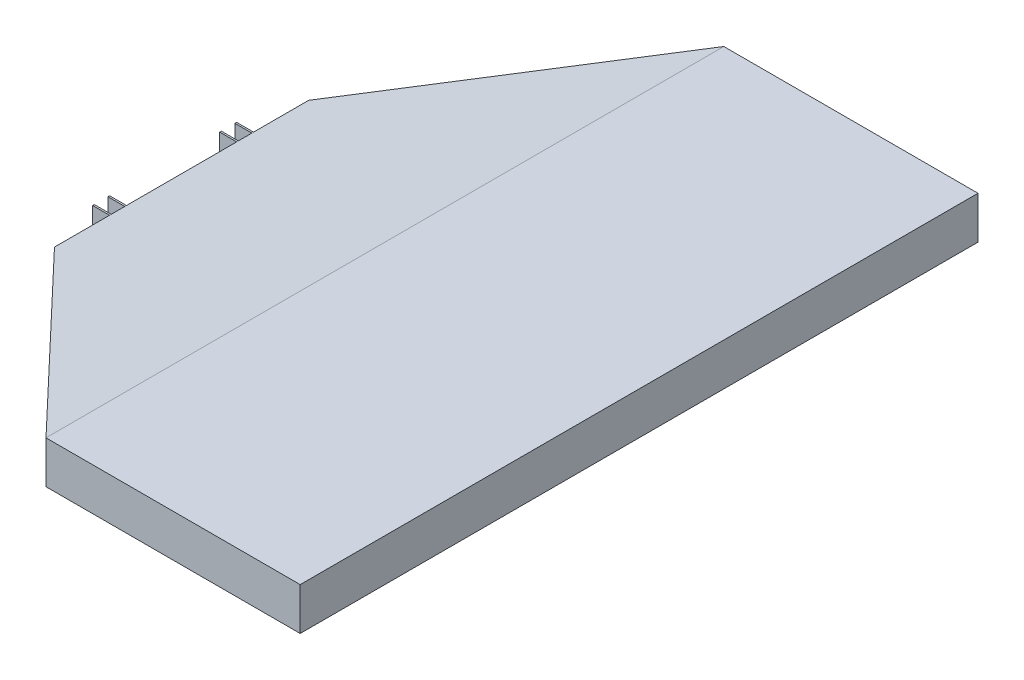
SolidWorks part; units mm, degrees
material "1060 Alloy"
ref_plane "Front Plane" through (0, 0, 0) normal (0, 0, 1) x (1, 0, 0)
ref_plane "Top Plane" through (0, 0, 0) normal (0, 1, 0) x (1, 0, 0)
ref_plane "Right Plane" through (0, 0, 0) normal (1, 0, 0) x (0, 0, -1)
sketch "Sketch1" plane through (0, 0, 0) normal (0, 1, 0) x (1, 0, 0)
  line L1 (3.5148, 13.895) -> (67.0148, 13.895)
  line L2 (3.5148, 13.895) -> (3.5148, -36.905)
  line L3 (3.5148, -36.905) -> (67.0148, -36.905)
  line L4 (67.0148, 13.895) -> (67.0148, -36.905)
  dimension "D1" = 63.5
  dimension "D2" = 50.8
extrude "Boss-Extrude1" add sketch "Sketch1" along normal blind 6.35
sketch "Sketch2" plane through (0, 0, 0) normal (0, 1, 0) x (1, 0, 0)
  line L0 (3.5148, 13.895) -> (3.5148, -36.905)
  line L1 (3.5148, -36.905) -> (-26.9652, -36.905)
  line L4 (-26.9652, -36.905) -> (-26.9652, -17.855)
  line L5 (-26.9652, -17.855) -> (3.5148, 13.895)
  dimension "D1" = 30.48
  dimension "D2" = 19.05
extrude "Boss-Extrude5" add sketch "Sketch2" along normal blind 6.35
sketch "Sketch7" plane through (0, 0, -13.895) normal (0, 0, -1) x (-1, 0, 0)
  line L0 (-3.5148, 6.35) -> (26.9652, 0)
  line L1 (26.9652, 0) -> (26.9652, 6.35)
  line L2 (26.9652, 6.35) -> (-3.5148, 6.35)
extrude "Cut-Extrude3" cut sketch "Sketch7" against normal blind 55.118
sketch "Sketch8" plane through (0, 0, 0) normal (0, -1, 0) x (-1, 0, 0)
  line L0 (26.9652, -17.855) -> (1.5652, -17.855)
  line L1 (1.5652, -17.855) -> (1.5652, -36.905)
  line L2 (26.9652, -36.905) -> (-67.0148, -36.905) construction
  line L3 (26.9652, -17.855) -> (26.9652, -36.905)
  line L4 (26.9652, -36.905) -> (1.5652, -36.905)
  dimension "D1" = 25.4
extrude "Boss-Extrude6" add sketch "Sketch8" along normal blind 2.54
sketch "Sketch11" plane through (0, -2.54, 0) normal (0, -1, 0) x (1, 0, 0)
  line L1 (-26.9652, 36.905) -> (-26.9652, 17.855) construction
  line L2 (-26.9652, 27.38) -> (-26.9652, 28.65)
  line L3 (-26.9652, 27.38) -> (-26.9652, 26.11)
  line L4 (-26.9652, 28.65) -> (-29.5052, 28.65)
  line L5 (-29.5052, 28.65) -> (-29.5052, 26.11)
  line L6 (-29.5052, 26.11) -> (-26.9652, 26.11)
  dimension "D1" = 1.27
  dimension "D2" = 1.27
  dimension "D3" = 2.54
extrude "Boss-Extrude9" add sketch "Sketch11" against normal blind 2.54
sketch "Sketch13" plane through (-29.5052, 0, 0) normal (-1, 0, 0) x (0, 0, 1)
  line L0 (27.38, 0) -> (26.364, 0)
  line L1 (26.11, 0) -> (28.65, 0) construction
  line L2 (27.38, 0) -> (28.396, 0)
  line L3 (26.364, 0) -> (26.364, -2.54)
  line L4 (28.65, -2.54) -> (26.11, -2.54) construction
  line L5 (26.364, -2.54) -> (27.38, -2.54)
  line L6 (27.38, -2.54) -> (28.396, -2.54)
  line L7 (28.396, -2.54) -> (28.396, 0)
  dimension "D1" = 1.016
  dimension "D2" = 1.016
extrude "Cut-Extrude5" cut sketch "Sketch13" against normal blind 2.54
sketch "Sketch14" plane through (0, -2.54, 0) normal (0, -1, 0) x (1, 0, 0)
  line L0 (-14.2652, 36.905) -> (-7.9152, 36.905)
  line L1 (-1.5652, 36.905) -> (-26.9652, 36.905) construction
  line L2 (-14.2652, 36.905) -> (-20.6152, 36.905)
  line L3 (-20.6152, 36.905) -> (-20.6152, 26.745)
  line L4 (-20.6152, 26.745) -> (-7.9152, 26.745)
  line L5 (-7.9152, 26.745) -> (-7.9152, 36.905)
  dimension "D1" = 6.35
  dimension "D2" = 6.35
  dimension "D3" = 10.16
extrude "Boss-Extrude10" add sketch "Sketch14" along normal blind 10.16
sketch "Sketch15" plane through (-20.6152, 0, 0) normal (-1, 0, 0) x (0, 0, 1)
  line L1 (36.905, -12.7) -> (26.745, -12.7) construction
  line L4 (28.015, -12.7) -> (28.015, -11.43)
  line L6 (36.905, -12.7) -> (36.905, -2.54) construction
  line L7 (28.015, -11.43) -> (36.905, -6.35)
  line L8 (28.015, -12.7) -> (36.905, -12.7)
  line L9 (36.905, -12.7) -> (36.905, -6.35)
  dimension "D3" = 1.27
extrude "Cut-Extrude6" cut sketch "Sketch15" against normal blind 12.7
sketch "Sketch16" plane through (0, 0, 17.855) normal (0, 0, -1) x (-1, 0, 0)
  line L0 (22.5202, -2.54) -> (22.5202, 0)
  line L1 (23.7902, -2.54) -> (22.5202, -2.54)
  line L2 (23.7902, -2.54) -> (25.0602, -2.54)
  line L3 (-3.5148, 0) -> (26.9652, 0) construction
  line L4 (22.5202, 0) -> (25.0602, 0)
  line L5 (25.0602, 0) -> (25.0602, -2.54)
  dimension "D1" = 1.27
  dimension "D2" = 1.27
extrude "Boss-Extrude11" add sketch "Sketch16" along normal blind 1.27
extrude "Cut-Extrude7" cut sketch "Sketch16<2>" along normal blind 1.016
sketch "Sketch16<2>" plane through (0, 0, 17.855) normal (0, 0, -1) x (-1, 0, 0) same geometry as "Sketch16"
sketch "Sketch18" plane through (0, 0, 17.855) normal (0, 0, -1) x (-1, 0, 0)
  line L2 (4.7402, -2.54) -> (3.4702, -2.54)
  line L3 (4.7402, -2.54) -> (6.0102, -2.54)
  line L4 (3.4702, -2.54) -> (3.4702, 0)
  line L5 (26.9652, 0) -> (1.5652, 0) construction
  line L6 (3.4702, 0) -> (6.0102, 0)
  line L7 (6.0102, 0) -> (6.0102, -2.54)
  dimension "D2" = 1.27
  dimension "D3" = 1.27
extrude "Boss-Extrude12" add sketch "Sketch18" along normal blind 15.494
extrude "Cut-Extrude8" cut sketch "Sketch18<2>" along normal blind 15.24
sketch "Sketch18<2>" plane through (0, 0, 17.855) normal (0, 0, -1) x (-1, 0, 0) same geometry as "Sketch18"
extrude "Boss-Extrude14" add sketch "Sketch18<4>" along normal blind 7.874
sketch "Sketch18<4>" plane through (0, 0, 17.855) normal (0, 0, -1) x (-1, 0, 0) same geometry as "Sketch18"
extrude "Cut-Extrude9" cut sketch "Sketch18<5>" along normal blind 7.62
sketch "Sketch18<5>" plane through (0, 0, 17.855) normal (0, 0, -1) x (-1, 0, 0) same geometry as "Sketch18"
sketch "Sketch19" plane through (0, 0, 2.361) normal (0, 0, -1) x (-1, 0, 0)
  circle A2 centre (4.7402, -1.27) radius 0.889
sketch "Sketch20" plane through (0, 0, 16.585) normal (0, 0, -1) x (-1, 0, 0)
  circle A0 centre (23.7902, -1.27) radius 0.889
extrude "Cut-Extrude12" cut sketch "Sketch20" against normal blind 0.762
extrude "Cut-Extrude13" cut sketch "Sketch19" against normal blind 11.938
sketch "Sketch21" plane through (0, -2.54, 0) normal (0, -1, 0) x (1, 0, 0)
  line L0 (-20.6152, 36.905) -> (-26.9652, 36.905) construction
  line L1 (-23.7902, 36.905) -> (-20.6152, 36.905)
  line L2 (-23.7902, 36.905) -> (-23.7902, 26.745)
  line L3 (-23.7902, 26.745) -> (-20.6152, 26.745)
  line L4 (-20.6152, 36.905) -> (-20.6152, 26.745)
  line L5 (-1.5652, 36.905) -> (-7.9152, 36.905) construction
  line L6 (-7.9152, 26.745) -> (-4.7402, 26.745)
  line L7 (-7.9152, 26.745) -> (-7.9152, 36.905)
  line L8 (-7.9152, 36.905) -> (-4.7402, 36.905)
  line L9 (-4.7402, 26.745) -> (-4.7402, 36.905)
extrude "Boss-Extrude15" add sketch "Sketch21" along normal blind 10.16
sketch "Sketch22" plane through (0, 0, 36.905) normal (0, 0, 1) x (1, 0, 0)
  line L0 (-23.7902, -12.7) -> (-20.6152, -6.35)
  line L1 (-20.6152, -6.35) -> (-20.6152, -12.7)
  line L2 (-20.6152, -12.7) -> (-23.7902, -12.7)
  line L3 (-7.9152, -6.35) -> (-4.7402, -12.7)
  line L4 (-4.7402, -12.7) -> (-7.9152, -12.7)
  line L5 (-7.9152, -12.7) -> (-7.9152, -6.35)
extrude "Cut-Extrude15" cut sketch "Sketch22" against normal blind 10.16
sketch "Sketch23" plane through (-20.6152, 0, 0) normal (-1, 0, 0) x (0, 0, 1)
  line L0 (28.015, -12.7) -> (26.745, -12.7)
  line L1 (26.745, -12.7) -> (26.745, -6.35)
  line L2 (26.745, -6.35) -> (36.905, -6.35)
  line L3 (36.905, -6.35) -> (28.015, -11.43)
  line L4 (28.015, -11.43) -> (28.015, -12.7)
extrude "Boss-Extrude16" add sketch "Sketch23" along normal blind 3.175
extrude "Boss-Extrude17" add sketch "Sketch23<2>" against normal blind 15.875
sketch "Sketch23<2>" plane through (-20.6152, 0, 0) normal (-1, 0, 0) x (0, 0, 1) same geometry as "Sketch23"
ref_plane "Plane1" through (41.6148, 0, 0) normal (1, 0, 0) x (0, 0, -1)
sketch "Sketch26" plane through (41.6148, 0, 0) normal (1, 0, 0) x (0, 0, -1)
  line L1 (-86.8949, -124.8661) -> (42.4872, -124.8661)
  line L2 (-86.8949, -124.8661) -> (-86.8949, 68.1832)
  line L3 (-86.8949, 68.1832) -> (42.4872, 68.1832)
  line L4 (42.4872, -124.8661) -> (42.4872, 68.1832)
extrude "Cut-Extrude16" cut sketch "Sketch26" along normal blind 154.178
mirror "Mirror1" about plane through (3.5148, 6.35, 36.905) normal (0, 0, -1) of "Cut-Extrude16", "Boss-Extrude17", "Boss-Extrude16", "Cut-Extrude15", "Boss-Extrude15", "Cut-Extrude13", "Cut-Extrude12", "Cut-Extrude9", "Boss-Extrude14", "Cut-Extrude8", "Boss-Extrude12", "Cut-Extrude7", "Boss-Extrude11", "Cut-Extrude6", "Boss-Extrude10", "Cut-Extrude5", "Boss-Extrude9", "Boss-Extrude6", "Cut-Extrude3", "Boss-Extrude5", "Boss-Extrude1"
sketch "Sketch27" plane through (0, 0, 0) normal (0, -1, 0) x (1, 0, 0)
  circle A0 centre (-2.2002, 6.298) radius 1.27
  circle A1 centre (-2.2002, 67.512) radius 1.27
  dimension "D5" = 2.54
extrude "Cut-Extrude18" cut sketch "Sketch27" against normal blind 3.81
fillet "Fillet1" radius 2.54 1 edges at (-14.2652, -12.7, 26.745)
fillet "Fillet2" radius 1.27 1 edges at (-14.2652, -12.7, 45.795)
